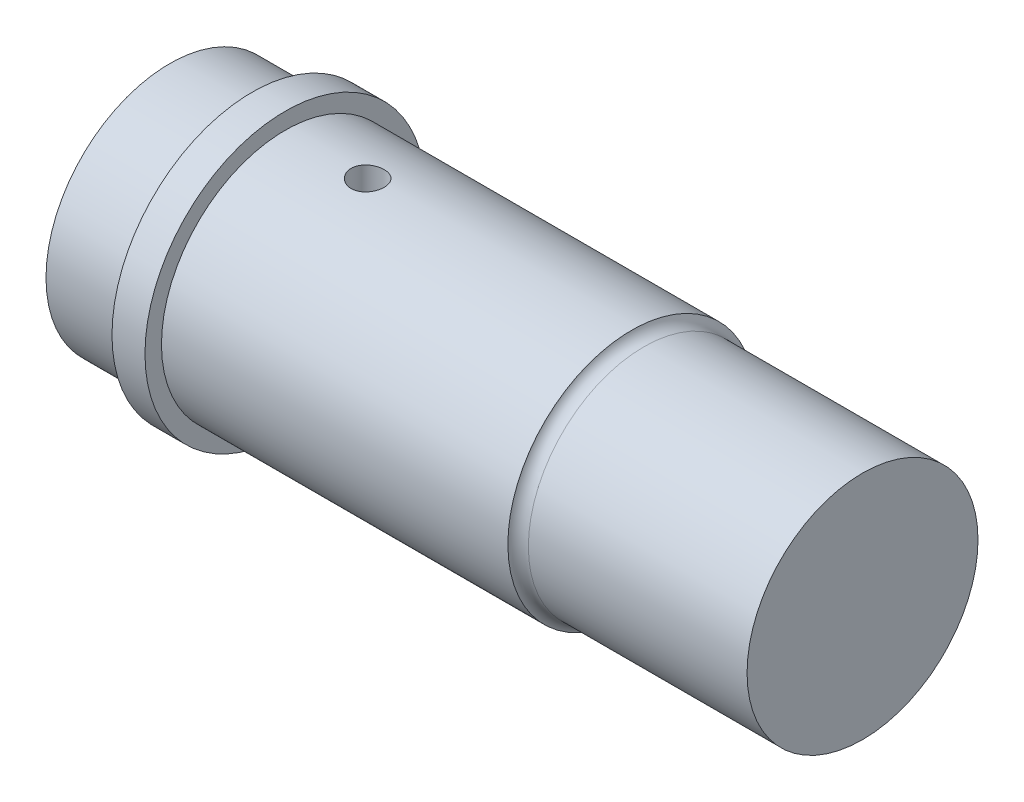
SolidWorks part; units mm, degrees
material "Plain Carbon Steel"
ref_plane "Front Plane" through (0, 0, 0) normal (0, 0, 1) x (1, 0, 0)
ref_plane "Top Plane" through (0, 0, 0) normal (0, 1, 0) x (1, 0, 0)
ref_plane "Right Plane" through (0, 0, 0) normal (1, 0, 0) x (0, 0, -1)
sketch "Sketch1" plane through (0, 0, 0) normal (1, 0, 0) x (0, 0, -1)
  circle A0 centre (0, 0) radius 7.5
  dimension "D1" = 15
extrude "Boss-Extrude1" add sketch "Sketch1" along normal blind 5
sketch "Sketch2" plane through (5, 0, 0) normal (1, 0, 0) x (0, 0, -1)
  circle A0 centre (0, 0) radius 8.5
  dimension "D1" = 17
extrude "Boss-Extrude2" add sketch "Sketch2" along normal blind 2
sketch "Sketch3" plane through (7, 0, 0) normal (1, 0, 0) x (0, 0, -1)
  circle A0 centre (0, 0) radius 7.5
  dimension "D1" = 15
extrude "Boss-Extrude3" add sketch "Sketch3" along normal blind 35
sketch "Sketch4" plane through (0, 0, 0) normal (-1, 0, 0) x (0, 0, 1)
  circle A0 centre (0, 0) radius 4
  dimension "D1" = 8
extrude "Cut-Extrude1" cut sketch "Sketch4" against normal blind 20.5
sketch "Sketch6" plane through (0, 0, 0) normal (-1, 0, 0) x (0, 0, 1)
  line L0 (0, -3.85) -> (0, 3.85) construction
  line L1 (-1.5, 3.25) -> (1.5, 3.25)
  line L2 (-1.5, 3.25) -> (-1.5, 4.75)
  line L3 (-1.5, 4.75) -> (1.5, 4.75)
  line L4 (1.5, 3.25) -> (1.5, 4.75)
  line L5 (-1.5, 3.25) -> (1.5, 4.75) construction
  line L6 (-1.5, 4.75) -> (1.5, 3.25) construction
  circle A0 centre (0, 0) radius 4 construction
  point P0 (0, 4)
  dimension "D1" = 3
  dimension "D2" = 1.5
extrude "Cut-Extrude2" cut sketch "Sketch6" against normal blind 20.5
ref_plane "Plane1" through (0, 7.5, 0) normal (0, 1, 0) x (1, 0, 0)
sketch "Sketch7" plane through (0, 7.5, 0) normal (0, 1, 0) x (1, 0, 0)
  line L0 (-3.85, 0) -> (3.85, 0) construction
  line L1 (0, -9.35) -> (0, 9.35) construction
  circle A0 centre (12, 0) radius 1
  dimension "D1" = 2
  dimension "D2" = 12
extrude "Cut-Extrude3" cut sketch "Sketch7" against normal up to next
sketch "Sketch8" plane through (42, 0, 0) normal (1, 0, 0) x (0, 0, -1)
  line L0 (0, 9.35) -> (0, -9.35) construction
  line L1 (-2.5, -9.5) -> (2.5, -9.5)
  line L2 (-2.5, -9.5) -> (-2.5, -5.5)
  line L3 (-2.5, -5.5) -> (2.5, -5.5)
  line L4 (2.5, -9.5) -> (2.5, -5.5)
  line L5 (-2.5, -9.5) -> (2.5, -5.5) construction
  line L6 (-2.5, -5.5) -> (2.5, -9.5) construction
  circle A0 centre (0, 0) radius 7.5 construction
  point P0 (0, -7.5)
  dimension "D1" = 5
  dimension "D2" = 2
extrude "Cut-Extrude5" cut sketch "Sketch8" along normal blind 19 from surface starting at face at (7, 0, -7.5)
sketch "Sketch9" plane through (42, 0, 0) normal (1, 0, 0) x (0, 0, -1)
  circle A0 centre (0, 0) radius 7.5
  circle A1 centre (0, 0) radius 7
  dimension "D1" = 15
  dimension "D2" = 14
extrude "Cut-Extrude6" cut sketch "Sketch9" against normal blind 14
fillet "Fillet1" radius 0.8 1 edges at (28, 0, -7)
ref_plane "Plane2" through (28, 0, 0) normal (1, 0, 0) x (0, 0, -1)
